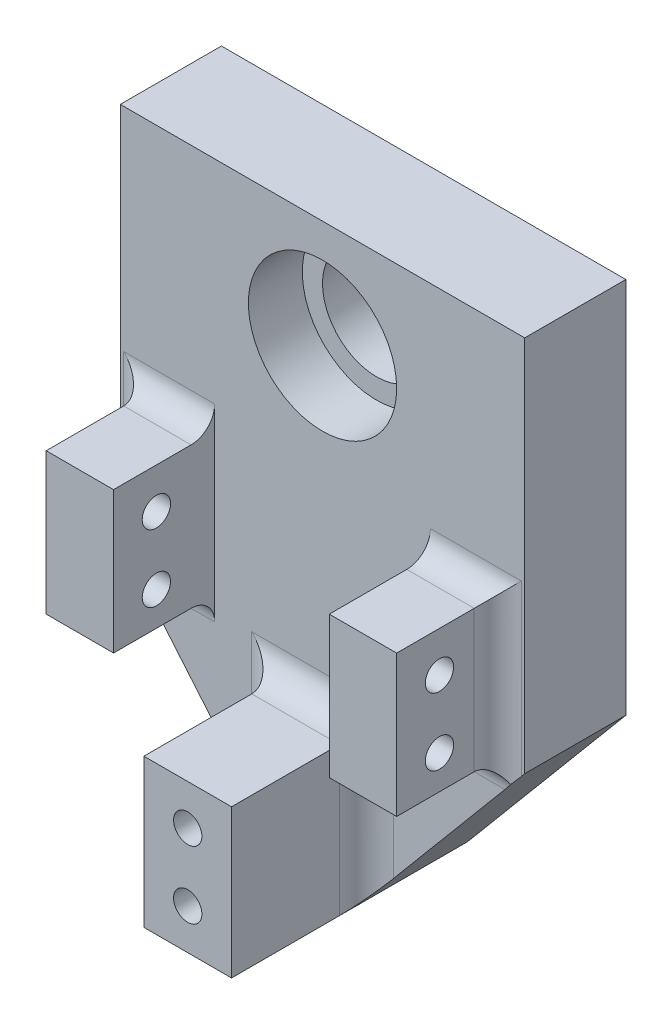
SolidWorks part; units mm, degrees
ref_plane "Front Plane" through (0, 0, 0) normal (0, 0, 1) x (1, 0, 0)
ref_plane "Top Plane" through (0, 0, 0) normal (0, 1, 0) x (1, 0, 0)
ref_plane "Right Plane" through (0, 0, 0) normal (1, 0, 0) x (0, 0, -1)
sketch "Sketch1" plane through (0, 0, 0) normal (0, 0, 1) x (1, 0, 0)
  line L1 (-30, -40) -> (30, -40)
  line L2 (-30, -40) -> (-30, 16)
  line L3 (-30, 16) -> (30, 16)
  line L4 (30, -40) -> (30, 16)
  circle A0 centre (0, 0) radius 11
  circle A3 centre (0, 0) radius 11 construction
  dimension "D1" = 22
  dimension "D2" = 22
  dimension "D3" = 60
  dimension "D4" = 16
  dimension "D5" = 30
  dimension "D6" = 40
extrude "Boss-Extrude1" add sketch "Sketch1" along normal blind 8
sketch "Sketch2" plane through (0, 0, 0) normal (0, 0, -1) x (-1, 0, 0)
  line L0 (-37.1992, 0) -> (52.0024, 0) construction
  line L1 (30, -40) -> (-30, -40) construction
  line L2 (30, 16) -> (30, -40) construction
  line L3 (-30, 16) -> (30, 16) construction
  line L4 (-30, -40) -> (-30, 16) construction
  line L5 (30, -40) -> (-30, -40)
  line L6 (30, 16) -> (30, -40)
  line L7 (-30, 16) -> (30, 16)
  line L8 (-30, -40) -> (-30, 16)
  circle A0 centre (0, 0) radius 8
  dimension "D1" = 16
extrude "Boss-Extrude2" add sketch "Sketch2" along normal blind 7
sketch "Sketch3" plane through (0, 0, 8) normal (0, 0, 1) x (1, 0, 0)
  line L0 (-16, -19) -> (-16, -40)
  line L1 (-16, -40) -> (-26, -40)
  line L2 (-26, -40) -> (-26, -19)
  line L3 (-26, -19) -> (-16, -19)
  line L4 (16, -19) -> (16, -40)
  line L5 (16, -40) -> (26, -40)
  line L6 (26, -40) -> (26, -19)
  line L7 (26, -19) -> (16, -19)
  line L8 (-21.8445, 35) -> (27.1513, 35) construction
  line L9 (-24.4362, -40) -> (27.9535, -40) construction
  dimension "D1" = 21
  dimension "D2" = 10
  dimension "D3" = 10
  dimension "D4" = 21
  dimension "D5" = 16
  dimension "D6" = 16
  dimension "D7" = 35
  dimension "D8" = 75
extrude "Boss-Extrude3" add sketch "Sketch3" along normal blind 15
sketch "Sketch4" plane through (-26, 0, 0) normal (-1, 0, 0) x (0, 0, 1)
  line L0 (16.65, -41.925) -> (16.65, -16.4347) construction
  line L1 (23, -19) -> (23, -40) construction
  line L2 (23, -40) -> (8, -40) construction
  circle A0 centre (16.65, -25) radius 2.1
  circle A1 centre (16.65, -35) radius 2.1
  dimension "D2" = 4.2
  dimension "D3" = 4.2
  dimension "D1" = 6.35
  dimension "D4" = 10
  dimension "D5" = 5
extrude "Cut-Extrude1" cut sketch "Sketch4" against normal through all
sketch "Sketch5" plane through (0, 0, 8) normal (0, 0, 1) x (1, 0, 0)
  line L0 (0, 0) -> (0, -62) construction
  line L1 (-16, -40) -> (16, -40) construction
  line L2 (-30, -40) -> (30, -40)
  line L3 (30, -40) -> (6.5, -68)
  line L4 (6.5, -68) -> (-6.5, -68)
  line L5 (-6.5, -68) -> (-30, -40)
  circle A0 centre (0, -52) radius 2.1
  circle A1 centre (0, -62) radius 2.1
  dimension "D3" = 10
  dimension "D1" = 4.2
  dimension "D2" = 4.2
  dimension "D4" = 12
  dimension "D5" = 6
  dimension "D6" = 13
  dimension "D7" = 6.5
extrude "Boss-Extrude4" add sketch "Sketch5" against normal through all
sketch "Sketch6" plane through (0, 0, -7) normal (0, 0, -1) x (-1, 0, 0)
  circle A0 centre (0, -52) radius 3.75
  circle A1 centre (0, -62) radius 3.75
  dimension "D1" = 7.5
  dimension "D2" = 7.5
extrude "Cut-Extrude2" [suppressed] cut sketch "Sketch6" against normal blind 5
fillet "Fillet2" radius 3.5 6 edges at (21, -19, 8) (26, -29.5, 8) (21, -40, 8) (-21, -19, 8) (-21, -40, 8) (-26, -29.5, 8)
sketch "Sketch7" plane through (0, 0, 8) normal (0, 0, 1) x (1, 0, 0)
  line L0 (-6.5, -68) -> (6.5, -68)
  line L1 (6.5, -68) -> (6.5, -46)
  line L2 (6.5, -46) -> (-6.5, -46)
  line L3 (-6.5, -46) -> (-6.5, -68)
  circle A0 centre (0, -52) radius 2.1 construction
  circle A1 centre (0, -62) radius 2.1 construction
  circle A2 centre (0, -62) radius 2.1
  circle A3 centre (0, -52) radius 2.1
  dimension "D1" = 6
extrude "Boss-Extrude5" add sketch "Sketch7" along normal blind 20
fillet "Fillet3" radius 4 3 edges at (-6.5, -57, 8) (6.5, -57, 8) (0, -46, 8)
equation "\"D6@Sketch3\"=\"D5@Sketch3\""
equation "\"D4@Sketch3\"=\"D1@Sketch3\""
equation "\"D2@Sketch5\"=\"D1@Sketch5\""
